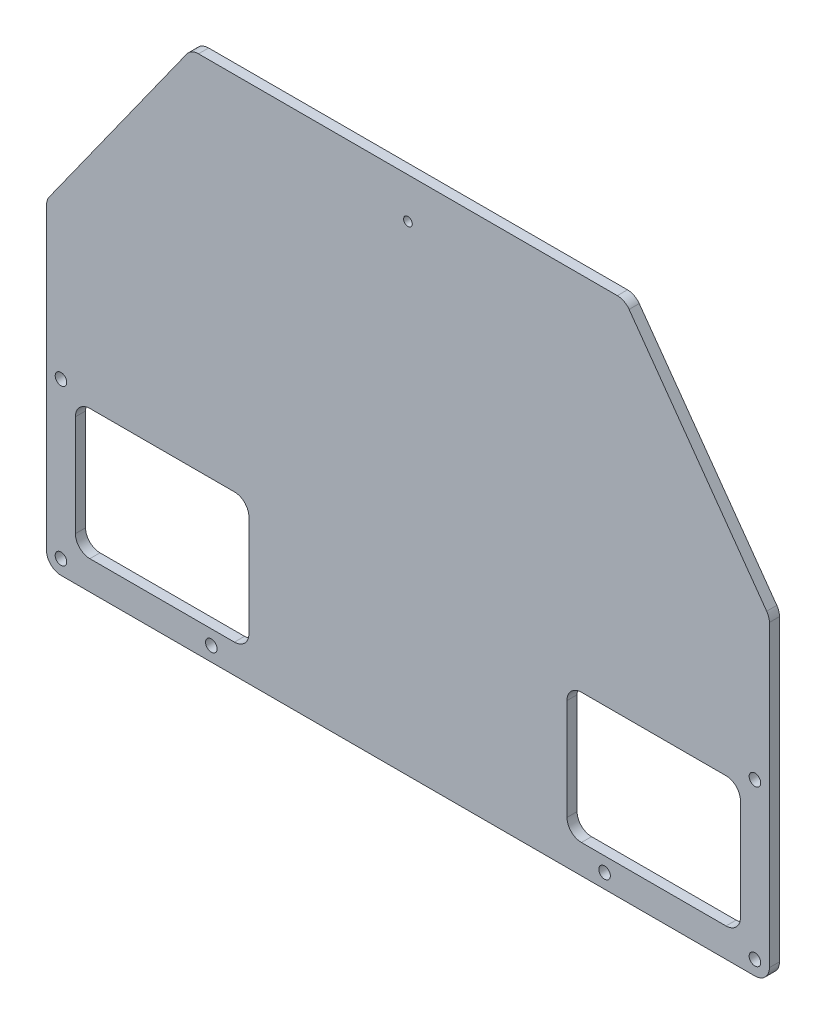
SolidWorks part; units mm, degrees
ref_plane "Plan de face" through (0, 0, 0) normal (0, 0, 1) x (1, 0, 0)
ref_plane "Plan de dessus" through (0, 0, 0) normal (0, 1, 0) x (1, 0, 0)
ref_plane "Plan de droite" through (0, 0, 0) normal (1, 0, 0) x (0, 0, -1)
sketch "Esquisse1" plane through (0, 0, 0) normal (0, 0, 1) x (1, 0, 0)
  line L1 (5, 0) -> (245, 0)
  line L2 (0, 5) -> (0, 305)
  line L3 (0, 305) -> (250, 305)
  line L4 (250, 5) -> (250, 305)
  arc A0 (250, 5) -> (245, 0) centre (245, 5) cw
  arc A1 (5, 0) -> (0, 5) centre (5, 5) cw
  point P7 (250, 0)
  point P10 (0, 0)
  dimension "D2" = 5
  dimension "D3" = 5
  dimension "D1" = 250
  dimension "D4" = 300
extrude "Boss.-Extru.1" add sketch "Esquisse1" along normal blind 3.5
sketch "Esquisse2" plane through (0, 0, 3.5) normal (0, 0, 1) x (1, 0, 0)
  line L0 (-19.0099, 5) -> (402.2953, 5) construction
  line L1 (5, 0) -> (245, 0) construction
  line L2 (5, -25.1291) -> (5, 139.966) construction
  line L3 (0, 305) -> (0, 5) construction
  line L4 (245, -22.1166) -> (245, 94.5536) construction
  line L5 (250, 5) -> (250, 305) construction
  line L6 (-9.3926, 58.8) -> (267.0784, 58.8) construction
  circle A0 centre (5, 5) radius 2
  circle A1 centre (245, 5) radius 2
  circle A2 centre (5, 58.8) radius 2
  circle A3 centre (245, 58.8) radius 2
  dimension "D1" = 4
  dimension "D2" = 4
  dimension "D7" = 4
  dimension "D8" = 4
  dimension "D3" = 5
  dimension "D4" = 5
  dimension "D5" = 5
  dimension "D6" = 53.8
extrude "Enlèv. mat.-Extru.1" cut sketch "Esquisse2" against normal through all
sketch "Esquisse3" plane through (0, 0, 3.5) normal (0, 0, 1) x (1, 0, 0)
  line L0 (-13.1091, 5) -> (277.0265, 5) construction
  line L1 (5, 0) -> (245, 0) construction
  line L2 (0, 305) -> (0, 5) construction
  circle A0 centre (57, 5) radius 2
  circle A1 centre (193, 5) radius 2
  dimension "D3" = 4
  dimension "D4" = 4
  dimension "D1" = 5
  dimension "D2" = 136
  dimension "D5" = 57
extrude "Enlèv. mat.-Extru.2" cut sketch "Esquisse3" against normal through all
sketch "Esquisse4" plane through (0, 0, 0) normal (0, 0, -1) x (-1, 0, 0)
  line L0 (-70, 15) -> (-70, 50)
  line L1 (-65, 55) -> (-15, 55)
  line L2 (-10, 50) -> (-10, 15)
  line L3 (-15, 10) -> (-65, 10)
  line L4 (-5, 0) -> (-245, 0) construction
  line L5 (0, 305) -> (0, 5) construction
  line L6 (-185, 10) -> (-235, 10)
  line L7 (-180, 15) -> (-180, 50)
  line L8 (-185, 55) -> (-235, 55)
  line L9 (-240, 15) -> (-240, 50)
  line L10 (-250, 5) -> (-250, 305) construction
  arc A0 (-70, 50) -> (-65, 55) centre (-65, 50) cw
  arc A1 (-15, 55) -> (-10, 50) centre (-15, 50) cw
  arc A2 (-70, 15) -> (-65, 10) centre (-65, 15) ccw
  arc A3 (-10, 15) -> (-15, 10) centre (-15, 15) cw
  arc A4 (-240, 50) -> (-235, 55) centre (-235, 50) cw
  arc A5 (-180, 50) -> (-185, 55) centre (-185, 50) ccw
  arc A6 (-240, 15) -> (-235, 10) centre (-235, 15) ccw
  arc A7 (-185, 10) -> (-180, 15) centre (-185, 15) ccw
  point P9 (-70, 55)
  point P12 (-10, 55)
  point P18 (-10, 10)
  point P27 (-240, 55)
  point P30 (-180, 55)
  point P35 (-180, 10)
  dimension "D4" = 5
  dimension "D10" = 5
  dimension "D1" = 10
  dimension "D2" = 60
  dimension "D3" = 45
  dimension "D5" = 10
  dimension "D6" = 10
  dimension "D7" = 45
  dimension "D8" = 60
  dimension "D9" = 10
extrude "Enlèv. mat.-Extru.3" cut sketch "Esquisse4" against normal through all
sketch "Esquisse5" plane through (0, 0, 3.5) normal (0, 0, 1) x (1, 0, 0)
  line L0 (0, 110) -> (50, 180)
  line L2 (50, 180) -> (200, 180)
  line L3 (200, 180) -> (250, 110)
  line L5 (125, 623.6506) -> (125, -13.6506) construction
  line L6 (250, 305) -> (0, 305) construction
  line L7 (5, 0) -> (245, 0) construction
  point P12 (125, 305)
  point P13 (125, 180)
  dimension "D1" = 150
  dimension "D2" = 180
  dimension "D3" = 110
  dimension "D4" = 110
extrude "Enlèv. mat.-Extru.4" cut sketch "Esquisse5" against normal through all and the other way through all
sketch "Esquisse6" plane through (0, 0, 3.5) normal (0, 0, 1) x (1, 0, 0)
  line L0 (50, 180) -> (200, 180) construction
  line L4 (125, 209.3374) -> (125, 98.3712) construction
  circle A0 centre (125, 166) radius 1.5
  point P2 (0, 0)
  dimension "D3" = 3
  dimension "D1" = 14
  dimension "D4" = 75
extrude "Enlèv. mat.-Extru.5" cut sketch "Esquisse6" against normal through all
fillet "Congé1" radius 5 4 edges at (250, 110, 1.75) (200, 180, 1.75) (50, 180, 1.75) (0, 110, 1.75)
